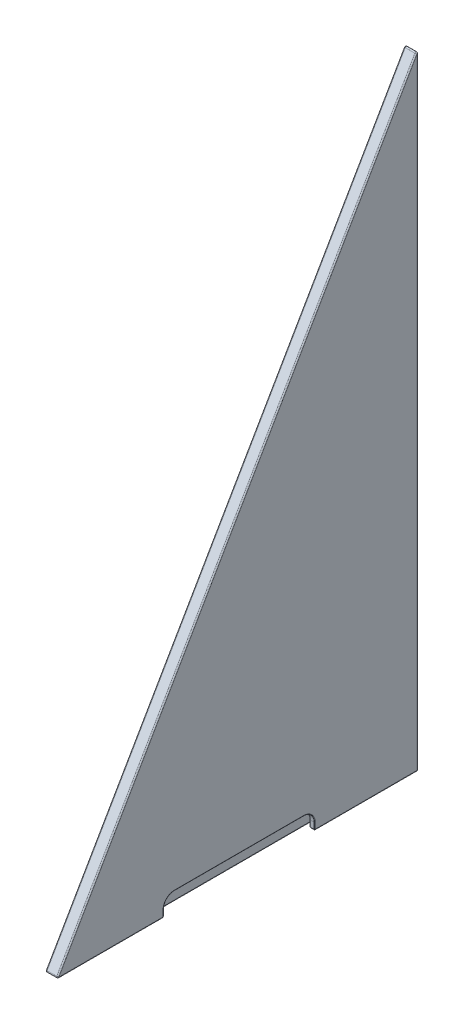
SolidWorks part; units mm, degrees
ref_plane "Front Plane" through (0, 0, 0) normal (0, 0, 1) x (1, 0, 0)
ref_plane "Top Plane" through (0, 0, 0) normal (0, 1, 0) x (1, 0, 0)
ref_plane "Right Plane" through (0, 0, 0) normal (1, 0, 0) x (0, 0, -1)
sketch "Sketch1" plane through (0, 0, 0) normal (1, 0, 0) x (0, 0, -1)
  line L0 (-301.715, -522.5857) -> (301.715, 522.5857)
  line L1 (301.715, -522.5857) -> (-301.715, -522.5857)
  line L2 (301.715, -522.5857) -> (301.715, 522.5857)
  line L3 (301.715, 522.5857) -> (-301.715, 522.5857) construction
  line L4 (-301.715, -522.5857) -> (-301.715, 522.5857) construction
  line L5 (301.715, -522.5857) -> (-301.715, 522.5857) construction
  line L6 (301.715, 522.5857) -> (-301.715, -522.5857) construction
  point P0 (0, 0)
  dimension "D1" = 603.43
  dimension "D2" = 60
extrude "Boss-Extrude1" add sketch "Sketch1" against normal blind 20
sketch "Sketch3" plane through (0, 0, 0) normal (1, 0, 0) x (0, 0, -1)
  line L0 (-301.715, -522.5857) -> (301.715, -522.5857) construction
  line L1 (-125, -522.5857) -> (125, -522.5857)
  line L2 (-125, -522.5857) -> (-125, -510.5857)
  line L3 (-107, -492.5857) -> (107, -492.5857)
  line L4 (125, -522.5857) -> (125, -510.5857)
  arc A0 (107, -492.5857) -> (125, -510.5857) centre (107, -510.5857) cw
  arc A1 (-125, -510.5857) -> (-107, -492.5857) centre (-107, -510.5857) cw
  point P4 (0, -522.5857)
  point P10 (125, -492.5857)
  point P13 (-125, -492.5857)
  dimension "D3" = 18
  dimension "D1" = 30
  dimension "D2" = 250
extrude "Cut-Extrude2" cut sketch "Sketch3" against normal blind 15
sketch "Sketch4" plane through (-15, 0, 0) normal (1, 0, 0) x (0, 0, -1)
  line L0 (-125, -522.5857) -> (125, -522.5857) construction
  line L1 (-135, -522.5857) -> (135, -522.5857)
  line L2 (-135, -522.5857) -> (-135, -505.5857)
  line L3 (-112, -482.5857) -> (112, -482.5857)
  line L4 (135, -522.5857) -> (135, -505.5857)
  arc A0 (112, -482.5857) -> (135, -505.5857) centre (112, -505.5857) cw
  arc A1 (-135, -505.5857) -> (-112, -482.5857) centre (-112, -505.5857) cw
  point P6 (0, -482.5857)
  point P10 (135, -482.5857)
  point P13 (-135, -482.5857)
  dimension "D3" = 23
  dimension "D1" = 270
  dimension "D2" = 40
extrude "Cut-Extrude3" cut sketch "Sketch4" along normal blind 7
sketch "Sketch5" plane through (0, 0, 0) normal (1, 0, 0) x (0, 0, -1)
  line L1 (301.715, -522.5857) -> (296.715, -522.5857)
  line L2 (301.715, -522.5857) -> (301.715, 522.5857)
  line L3 (301.715, 522.5857) -> (296.715, 522.5857)
  line L4 (296.715, -522.5857) -> (296.715, 522.5857)
  dimension "D1" = 5
extrude "Cut-Extrude4" cut sketch "Sketch5" against normal up to surface (20 mm away) up to face at (-20, -174.1952, -100.5717)
fillet "Fillet1" radius 1 20 edges at (-8, -514.0857, -135) (-8, -489.3223, -128.2635) (-8, -482.5857, 0) (-8, -514.0857, 135) (0, -516.5857, -125) (0, -497.8578, -119.7279) (0, -516.5857, 125) (0, -497.8578, 119.7279) (-8, -516.5857, -125) (-8, -497.8578, -119.7279) (-8, -516.5857, 125) (-8, -497.8578, 119.7279) (-15, -514.0857, -135) (-15, -489.3223, -128.2635) (-15, -514.0857, 135) (-15, -489.3223, 128.2635) (-8, -489.3223, 128.2635) (0, -492.5857, 0) (-8, -492.5857, 0) (-15, -482.5857, 0)
fillet "Fillet2" radius 2 25 edges at (0, -4.3301, -296.715) (-20, -4.3301, -296.715) (-10, -522.5857, -296.715) (-20, -522.5857, 2.5) (0, -522.5857, 213.8575) (-0.2929, -522.5857, 125.2929) (-4, -522.5857, 125) (-7.7071, -522.5857, 125.2929) (-8, -522.5857, 130) (-8.2929, -522.5857, 134.7071) (-11.5, -522.5857, 135) (-14.7071, -522.5857, 134.7071) (-15, -522.5857, 0) (-14.7071, -522.5857, -134.7071) (-11.5, -522.5857, -135) (-8.2929, -522.5857, -134.7071) (-8, -522.5857, -130) (-7.7071, -522.5857, -125.2929) (-4, -522.5857, -125) (-0.2929, -522.5857, -125.2929) (0, -522.5857, -211.3575) (0, -4.3301, 2.5) (-10, -522.5857, 301.715) (-20, -4.3301, 2.5) (-10, 513.9255, -296.715)
